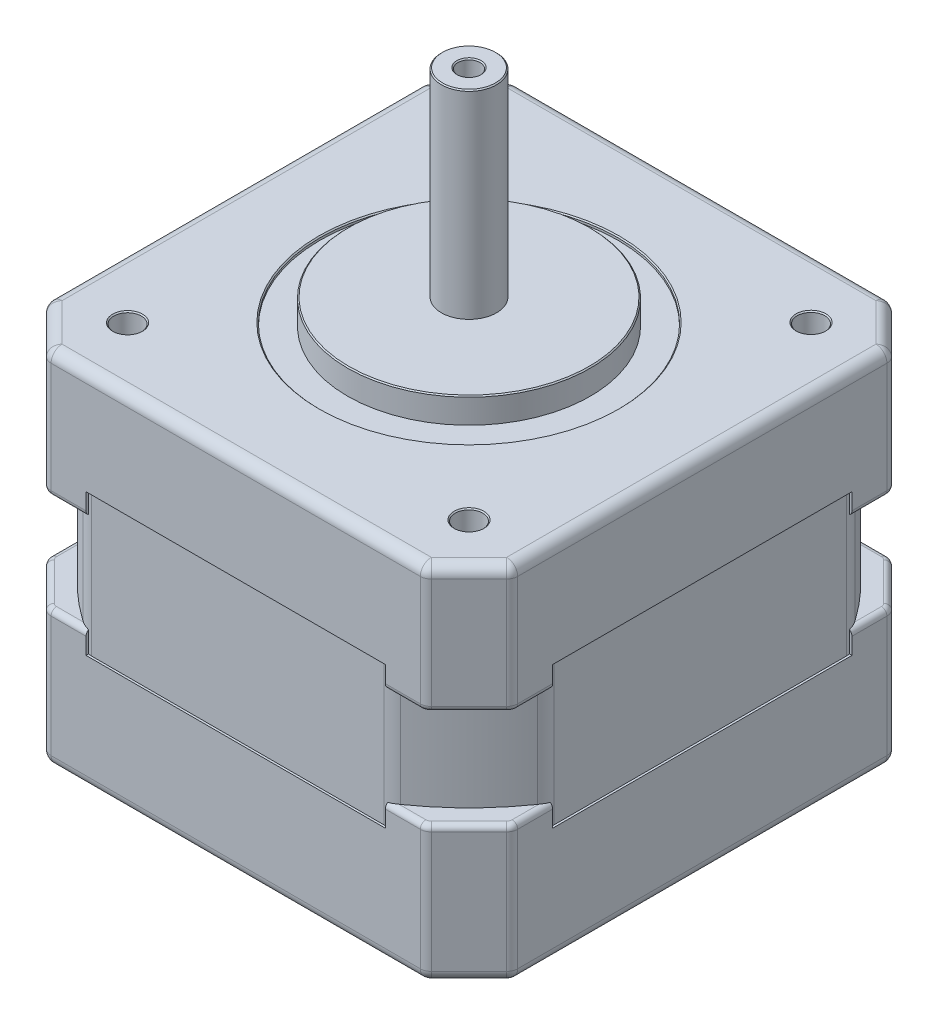
SolidWorks part; units mm, degrees
ref_plane "Front Plane" through (0, 0, 0) normal (0, 0, 1) x (1, 0, 0)
ref_plane "Top Plane" through (0, 0, 0) normal (0, 1, 0) x (1, 0, 0)
ref_plane "Right Plane" through (0, 0, 0) normal (1, 0, 0) x (0, 0, -1)
sketch "Sketch1" plane through (0, 0, 0) normal (0, 1, 0) x (1, 0, 0)
  line L0 (0, 21.15) -> (0, 0) construction
  line L1 (-21.15, 21.15) -> (-21.15, -21.15)
  line L2 (-21.15, -21.15) -> (21.15, -21.15)
  line L3 (-21.15, 21.15) -> (21.15, 21.15)
  line L4 (21.15, -21.15) -> (21.15, 21.15)
  line L5 (21.15, 0) -> (0, 0) construction
  line L6 (21.15, 21.15) -> (0, 0) construction
  line L7 (0, 0) -> (0, -21.15) construction
  circle A0 centre (15.5, 15.5) radius 1.25
  circle A1 centre (-15.4497, 15.5) radius 1.25
  circle A2 centre (-15.4497, -15.5) radius 1.25
  circle A3 centre (15.5, -15.5) radius 1.25
  dimension "D1" = 42.3
  dimension "D3" = 2.5
  dimension "D2" = 31
extrude "Boss-Extrude1" add sketch "Sketch1" against normal blind 32.8
chamfer "Chamfer1" distance 4 angle 45 4 edges at (21.15, -16.4, 21.15) (-21.15, -16.4, 21.15) (-21.15, -16.4, -21.15) (21.15, -16.4, -21.15)
sketch "Sketch2" plane through (0, 0, 0) normal (0, 1, 0) x (1, 0, 0)
  circle A0 centre (0, 0) radius 11
  dimension "D1" = 22
extrude "Boss-Extrude2" add sketch "Sketch2" along normal blind 2
sketch "Sketch6" plane through (0, -32.8, 0) normal (0, -1, 0) x (1, 0, 0)
  line L0 (-17.15, 21.15) -> (17.15, 21.15) construction
  line L1 (-21.15, -17.15) -> (-21.15, 17.15) construction
  line L2 (-17.15, 21.15) -> (-21.15, 17.15) construction
  line L3 (-17.15, 21.15) -> (-21.15, 17.15)
  line L4 (-21.15, 13.5626) -> (-21.15, 17.15)
  line L5 (-17.15, 21.15) -> (-13.5626, 21.15)
  arc A0 (-13.5626, 21.15) -> (-21.15, 13.5626) centre (0, 0) ccw
  dimension "D1" = 25.125
extrude "Cut-Extrude2" cut sketch "Sketch6" against normal offset from surface (8.85 mm away) 11.5 from offset 12.45 up to face at (15.5, 0, 16.75) offset against normal yes
pattern_circular "CirPattern1" count 4 over 360 about axis through (0, 10.7303, 0) along (0, -1, 0) of "Cut-Extrude2"
sketch "Sketch7" plane through (-21.15, 0, 0) normal (-1, 0, 0) x (0, 0, 1)
  line L0 (13.5626, -11.5) -> (13.5626, -20.35) construction
  line L1 (-13.5626, -9.5) -> (13.5626, -9.5)
  line L2 (-13.5626, -9.5) -> (-13.5626, -11.5)
  line L3 (-13.5626, -22.35) -> (13.5626, -22.35)
  line L4 (13.5626, -9.5) -> (13.5626, -11.5)
  line L5 (-13.5626, -11.5) -> (-13.5626, -20.35) construction
  line L6 (-17.15, -11.5) -> (-13.5626, -11.5) construction
  line L7 (-13.5626, -20.35) -> (-17.15, -20.35) construction
  line L8 (-21.15, -11.5) -> (-13.5626, -11.5) construction
  line L9 (-17.3563, -11.5) -> (-13.5626, -11.5)
  line L10 (-17.3563, -11.5) -> (-17.3563, -20.35)
  line L11 (-17.3563, -20.35) -> (-13.5626, -20.35)
  line L12 (19.15, -11.5) -> (19.15, -20.35)
  line L13 (21.15, -20.35) -> (17.15, -20.35) construction
  line L14 (13.5626, -11.5) -> (19.15, -11.5)
  line L15 (-13.5626, -20.35) -> (-13.5626, -22.35)
  line L16 (13.5626, -20.35) -> (13.5626, -22.35)
  line L17 (13.5626, -20.35) -> (19.15, -20.35)
  dimension "D1" = 2
  dimension "D2" = 2
extrude "Cut-Extrude3" cut sketch "Sketch7" against normal blind 0.2
pattern_circular "CirPattern2" count 4 over 360 about axis through (0, 2, 0) along (0, -1, 0) of "Cut-Extrude3"
sketch "Sketch3" plane through (0, 0, 0) normal (0, 1, 0) x (1, 0, 0)
  circle A0 centre (0, 0) radius 2.5
  dimension "D1" = 5
extrude "Boss-Extrude3" add sketch "Sketch3" along normal blind 20
sketch "Sketch8" plane through (0, -32.8, 0) normal (0, -1, 0) x (1, 0, 0)
  circle A0 centre (15.5, -15.5) radius 3.075
  circle A1 centre (15.5, 15.5) radius 3.075
  circle A2 centre (-15.4497, 15.5) radius 3.075
  circle A3 centre (-15.4497, -15.5) radius 3.075
  dimension "D1" = 6.15
extrude "Cut-Extrude4" cut sketch "Sketch8" against normal blind 2
sketch "Sketch9" plane through (0, -32.8, 0) normal (0, -1, 0) x (1, 0, 0)
  circle A0 centre (0, 0) radius 4.625
  dimension "D1" = 9.25
extrude "Cut-Extrude5" cut sketch "Sketch9" against normal blind 3
sketch "Sketch10" plane through (0, 0, -21.15) normal (0, 0, -1) x (-1, 0, 0)
  line L0 (-13.5626, -22.35) -> (13.5626, -22.35) construction
  line L1 (-4.1, -30.55) -> (4.1, -30.55)
  line L2 (-4.1, -30.55) -> (-4.1, -22.35)
  line L3 (-4.1, -22.35) -> (4.1, -22.35)
  line L4 (4.1, -30.55) -> (4.1, -22.35)
  line L5 (-4.1, -30.55) -> (4.1, -22.35) construction
  line L6 (-4.1, -22.35) -> (4.1, -30.55) construction
  line L7 (0, -11.5) -> (0, -20.35) construction
  point P0 (0, -26.45)
  dimension "D1" = 8.2
extrude "Cut-Extrude6" cut sketch "Sketch10" against normal blind 0.5
sketch "Sketch11" plane through (0, 0, 0) normal (0, 1, 0) x (1, 0, 0)
  circle A0 centre (0, 0) radius 11 construction
  circle A1 centre (0, 0) radius 11
  circle A2 centre (0, 0) radius 13.5
  dimension "D1" = 2.5
extrude "Cut-Extrude7" cut sketch "Sketch11" against normal blind 0.3
fillet "Fillet2" radius 2 8 edges at (-13.8695, -15.925, -20.95) (13.8695, -15.925, -20.95) (20.95, -15.925, -13.8695) (20.95, -15.925, 13.8695) (13.8695, -15.925, 20.95) (-13.8695, -15.925, 20.95) (-20.95, -15.925, 13.8695) (-20.95, -15.925, -13.8695)
fillet "Fillet1" radius 1 32 edges at (0, 0, 21.15) (0, -32.8, 21.15) (19.15, 0, -19.15) (19.15, -32.8, -19.15) (17.15, -5.75, -21.15) (17.15, -26.575, -21.15) (0, 0, -21.15) (0, -32.8, -21.15) (-17.15, -5.75, -21.15) (-17.15, -26.575, -21.15) (-19.15, 0, -19.15) (-19.15, -32.8, -19.15) (-21.15, -5.75, -17.15) (-21.15, -26.575, -17.15) (-21.15, 0, 0) (-21.15, -32.8, 0) (-21.15, -5.75, 17.15) (-21.15, -26.575, 17.15) (-19.15, 0, 19.15) (-17.15, -5.75, 21.15) (-17.15, -26.575, 21.15) (-19.15, -32.8, 19.15) (21.15, -5.75, -17.15) (21.15, -26.575, -17.15) (21.15, -32.8, 0) (21.15, 0, 0) (17.15, -5.75, 21.15) (17.15, -26.575, 21.15) (19.15, 0, 19.15) (21.15, -5.75, 17.15) (21.15, -26.575, 17.15) (19.15, -32.8, 19.15)
fillet "Fillet3" radius 0.5 40 edges at (21.15, -11.5, -15.1492) (21.0739, -11.5, -17.1185) (15.1492, -11.5, -21.15) (17.1185, -11.5, -21.0739) (15.1492, -20.35, -21.15) (17.1185, -20.35, -21.0739) (19.15, -20.35, -19.15) (21.0739, -20.35, -17.1185) (15.1492, -11.5, 21.15) (17.1185, -11.5, 21.0739) (21.15, -11.5, 15.1492) (21.0739, -11.5, 17.1185) (21.15, -20.35, 15.1492) (21.0739, -20.35, 17.1185) (15.1492, -20.35, 21.15) (17.1185, -20.35, 21.0739) (-21.15, -20.35, -15.1492) (-21.0739, -20.35, -17.1185) (-15.1492, -20.35, -21.15) (-17.1185, -20.35, -21.0739) (-15.1492, -20.35, 21.15) (-17.1185, -20.35, 21.0739) (-21.15, -20.35, 15.1492) (-21.0739, -20.35, 17.1185) (-21.15, -11.5, 15.1492) (-21.0739, -11.5, 17.1185) (-15.1492, -11.5, 21.15) (-17.1185, -11.5, 21.0739) (-15.1492, -11.5, -21.15) (-17.1185, -11.5, -21.0739) (-21.15, -11.5, -15.1492) (-21.0739, -11.5, -17.1185) (19.15, -11.5, -19.15) (21.15, -20.35, -15.1492) (19.15, -11.5, 19.15) (19.15, -20.35, 19.15) (-19.15, -20.35, -19.15) (-19.15, -20.35, 19.15) (-19.15, -11.5, 19.15) (-19.15, -11.5, -19.15)
chamfer "Chamfer2" distance 0.1 angle 45 6 edges at (0, 2, 11) (0, 0, 13.5) (-15.4497, 0, 16.75) (-15.4497, 0, -14.25) (15.5, 0, -14.25) (15.5, 0, 16.75)
sketch "Sketch12" plane through (0, 20, 0) normal (0, 1, 0) x (1, 0, 0)
  circle A0 centre (0, 0) radius 1
  dimension "D1" = 2
extrude "Cut-Extrude8" cut sketch "Sketch12" against normal blind 2.5
chamfer "Chamfer3" distance 0.1 angle 45 2 edges at (0, 20, 2.5) (0, 20, 1)
chamfer "Chamfer4" distance 0.3 angle 45 5 edges at (15.5, -32.8, -18.575) (15.5, -32.8, 12.425) (-15.4497, -32.8, 12.425) (-15.4497, -32.8, -18.575) (0, -32.8, -4.625)
sketch "Sketch13" plane through (0, 0, -20.65) normal (0, 0, -1) x (-1, 0, 0)
  line L0 (-2.025, -29.05) -> (2.025, -29.05) construction
  line L4 (-4.1, -30.55) -> (4.1, -30.55) construction
  line L8 (0, -29.8) -> (0, -32.5) construction
  circle A0 centre (-2.025, -29.05) radius 0.65
  circle A1 centre (-0.675, -29.05) radius 0.65
  circle A2 centre (0.675, -29.05) radius 0.65
  circle A3 centre (2.025, -29.05) radius 0.65
  point P8 (0, -29.05)
  dimension "D1" = 1.3
  dimension "D3" = 1.35
  dimension "D2" = 1.5
  dimension "D4" = 1.35
  dimension "D5" = 1.35
extrude "Boss-Extrude5" add sketch "Sketch13" along normal blind 5.5
sketch "Sketch5" plane through (-12.85, -32.8, 0) normal (0, 1, 0) x (0, 0, -1)
  line L0 (-20.15, -7.0234) -> (20.15, -7.0234) construction
  line L1 (20.15, 3.8858) -> (20.15, -29.5858) construction
  line L2 (-20.15, -29.5858) -> (-20.15, 3.8858) construction
  text T0 "http://multilogica-shop.com\r\nMOTOR\r\nPASSO A PASSO\r\nCód:MOT0030033\r\n" font "Century Gothic" height 1.5
extrude "Cut-Extrude1" cut sketch "Sketch5" along normal blind 0.3
equation "\"D2@Sketch7\"=\"D1@Sketch7\""
